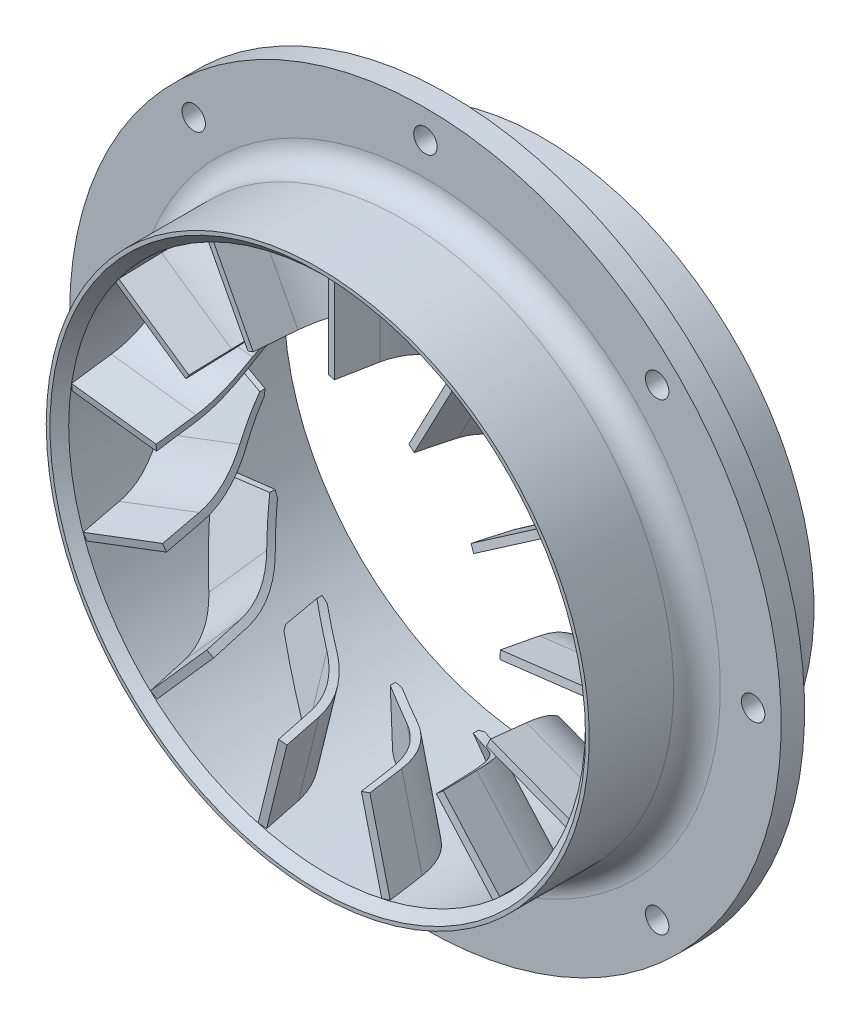
SolidWorks part; units mm, degrees
note: '?' marks a value the reader was unsure of.
material "AISI Type 316L stainless steel"
ref_plane "Front Plane" through (0, 0, 0) normal (0, 0, 1) x (1, 0, 0)
ref_plane "Top Plane" through (0, 0, 0) normal (0, 1, 0) x (1, 0, 0)
ref_plane "Right Plane" through (0, 0, 0) normal (1, 0, 0) x (0, 0, -1)
sketch "Sketch1" plane through (0, 0, 0) normal (1, 0, 0) x (0, 0, -1)
  line L0 (0, 0) -> (-39.6202, 0) construction
  line L1 (-10, 29) -> (0, 29)
  line L2 (0, 37.1787) -> (0, 0) construction
  line L3 (-24, 29) -> (-15, 29)
  line L4 (-24, 29) -> (-24, 27.6)
  line L5 (-24, 27.6) -> (0, 27.6)
  line L6 (0, 29) -> (0, 27.6)
  line L8 (-12.5, 31.5) -> (-12.5, 38)
  line L9 (-12.5, 38) -> (-10, 38)
  line L10 (-10, 29) -> (-10, 38)
  arc A0 (-12.5, 31.5) -> (-15, 29) centre (-15, 31.5) cw
  dimension "D7" = 2.5
  dimension "D1" = 55.2
  dimension "D2" = 58
  dimension "D3" = 24
  dimension "D4" = 2.5
  dimension "D5" = 10
  dimension "D6" = 76
revolve "Revolve1" add sketch "Sketch1" angle 360 about L0
hole_wizard "M3x0.5 Tapped Hole1" positions "Sketch3" profile "Sketch2" tap size "M3x0.5" standard "Ansi Metric"
sketch "Sketch3" plane through (0, 0, 12.5) normal (0, 0, 1) x (1, 0, 0)
  point P0 (0, 35)
  dimension "D1" = 35
sketch "Sketch2" plane through (0, 35, 12.5) normal (1, 0, 0) x (0, -1, 0)
  line L0 (0, 0) -> (0, 8.2511)
  line L1 (0, 8.2511) -> (1.25, 7.5)
  line L2 (1.25, 7.5) -> (1.25, 0)
  line L5 (1.25, 0) -> (0, 0)
  line L10 (0, 8.2511) -> (-1.25, 7.5) construction
  line L11 (0, -6.35) -> (0, 107.95) construction
  dimension "Tap Drill Dia." = 2.5
  dimension "Tap Drill Depth" = 7.5
  dimension "Drill Angle" = 118
ref_axis "Axis1" through (0, 0, -1.2) along (0, 0, 1)?
pattern_circular "CirPattern1" count 8 over 360 about axis through (0, 0, 0) along (0, 0, 1) of "M3x0.5 Tapped Hole1"
sketch "Sketch4" plane through (0, 0, 0) normal (0, 1, 0) x (1, 0, 0)
  line L0 (0, -22.8611) -> (0.7258, -18.7451)
  line L1 (0, 1.2) -> (0, -25.2) construction
  line L2 (4.6042, -13.2061) -> (12.13, -8.8611)
  line L4 (0.7878, -23) -> (1.5136, -18.884)
  line L5 (5.0042, -13.8989) -> (12.53, -9.5539)
  line L6 (0.7878, -23) -> (0, -22.8611)
  line L7 (12.53, -9.5539) -> (12.13, -8.8611)
  line L8 (-29, -24) -> (29, -24) construction
  arc A0 (0.7258, -18.7451) -> (4.6042, -13.2061) centre (8.6042, -20.1343) cw
  arc A1 (1.5136, -18.884) -> (5.0042, -13.8989) centre (8.6042, -20.1343) cw
  dimension "D5" = 8
  dimension "D1" = 1
  dimension "D2" = 10
  dimension "D3" = 60
  dimension "D4" = 14
  dimension "D7" = 12.53
  dimension "D6" = 0.8
extrude "fin" add sketch "Sketch4" along normal up to surface (27.5888 mm away) separate body
sketch "Sketch5" plane through (0, 0, 0) normal (0, 0, 1) x (1, 0, 0)
  line L0 (0, 0) -> (12.8264, 24.4386) construction
  line L3 (0, 18.5) -> (0, 27.6)
  line L4 (12.8264, 24.4386) -> (8.5974, 16.3809)
  arc A0 (8.5974, 16.3809) -> (0, 18.5) centre (0, 0) ccw
  circle A1 centre (0, 0) radius 27.6 construction
  arc A2 (0, 27.6) -> (12.8264, 24.4386) centre (0, 0) ccw
  dimension "D1" = 37
  dimension "D2" = 27.692
extrude "fin cut" cut sketch "Sketch5" along normal through all
pattern_circular "CirPattern5" count 13 over 360 about axis through (0, 0, 0) along (0, 0, 1) of bodies 105
chamfer "Chamfer1" distance 1 angle 45 1 edges at (-27.6, 0, 24)
sketch "Sketch6" plane through (0, 0, 0) normal (1, 0, 0) x (0, 0, -1)
  line L0 (0, 0) -> (-48.6796, 0) construction
  line L1 (0, 0) -> (-24, 0)
  line L2 (-24, 0) -> (-24, 18.5)
  line L3 (-24, 29) -> (-24, -29) construction
  line L4 (-24, 18.5) -> (-11.26, 18.5)
  line L5 (-11.26, 18.5) -> (-8.76, 27.6)
  line L6 (0, 27.6) -> (-23, 27.6) construction
  line L7 (-8.76, 27.6) -> (0, 27.6)
  line L8 (0, -29) -> (0, 29) construction
  line L9 (0, 27.6) -> (0, 0)
  dimension "D1" = 37
  dimension "D2" = 15.24
  dimension "D3" = 2.5
revolve "Cut-Revolve1" cut sketch "Sketch6" angle 360 about L0
